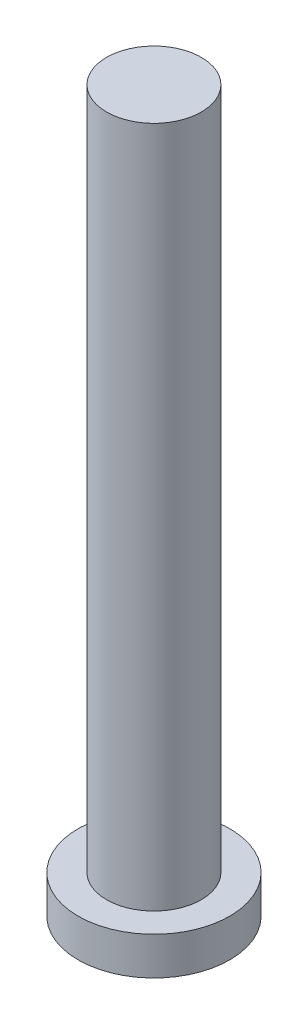
SolidWorks part; units mm, degrees
ref_plane "Front Plane" through (0, 0, 0) normal (0, 0, 1) x (1, 0, 0)
ref_plane "Top Plane" through (0, 0, 0) normal (0, 1, 0) x (1, 0, 0)
ref_plane "Right Plane" through (0, 0, 0) normal (1, 0, 0) x (0, 0, -1)
sketch "Sketch1" plane through (0, 0, 0) normal (0, 1, 0) x (1, 0, 0)
  circle A0 centre (0, 0) radius 2.54
  dimension "D1" = 5.08
extrude "Boss-Extrude1" add sketch "Sketch1" along normal blind 1.27
sketch "Sketch2" plane through (0, 1.27, 0) normal (0, 1, 0) x (1, 0, 0)
  circle A0 centre (0, 0) radius 1.5875
  dimension "D1" = 3.175
extrude "Boss-Extrude2" add sketch "Sketch2" along normal blind 22.86
